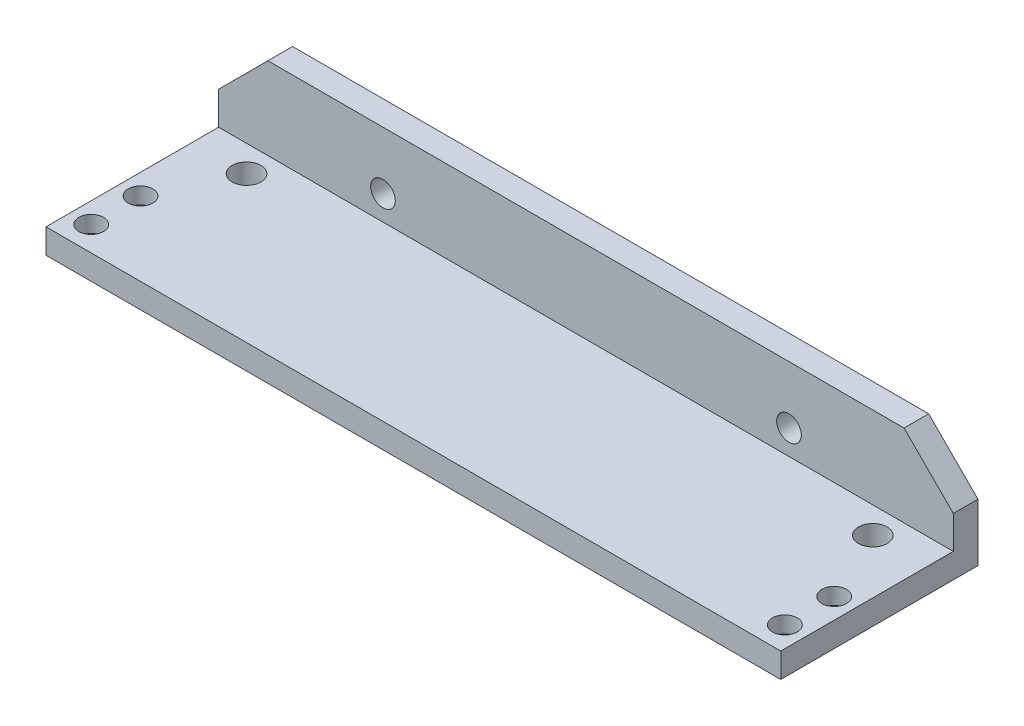
SolidWorks part; units mm, degrees
material "7075-T6, Plate (SS)"
ref_plane "Front Plane" through (0, 0, 0) normal (0, 0, 1) x (1, 0, 0)
ref_plane "Top Plane" through (0, 0, 0) normal (0, 1, 0) x (1, 0, 0)
ref_plane "Right Plane" through (0, 0, 0) normal (1, 0, 0) x (0, 0, -1)
sketch "Sketch1" plane through (0, 0, 0) normal (0, 0, 1) x (1, 0, 0)
  line L0 (-38.2511, 8.8926) -> (-38.2511, -1.1074)
  line L1 (-38.2511, -1.1074) -> (51.1489, -1.1074)
  line L2 (51.1489, -1.1074) -> (51.1489, 8.8926)
  line L3 (51.1489, 8.8926) -> (-38.2511, 8.8926)
  line L4 (-38.2511, -1.1074) -> (-38.2511, -4.1074)
  line L5 (-38.2511, -4.1074) -> (51.1489, -4.1074)
  line L6 (51.1489, -4.1074) -> (51.1489, -1.1074)
  line L7 (-38.2511, 2.8926) -> (-32.2511, 8.8926)
  line L8 (51.1489, 2.8926) -> (45.1489, 8.8926)
  circle A0 centre (-18.2511, 1.8926) radius 1.5
  circle A1 centre (31.1489, 1.8926) radius 1.5
  dimension "D2" = 3
  dimension "D3" = 3
  dimension "D1" = 89.4
  dimension "D4" = 3
  dimension "D5" = 10
  dimension "D6" = 3
  dimension "D7" = 3
  dimension "D8" = 20
  dimension "D9" = 20
  dimension "D10" = 4
  dimension "D11" = 6
  dimension "D12" = 6
  dimension "D13" = 6
extrude "Boss-Extrude1" add sketch "Sketch1" along normal blind 3 contours L2 L3 L0 L1 A1 A0 region at (6.4489, 3.7981, 0)
extrude "Boss-Extrude2" add sketch "Sketch1<3>" along normal blind 24 contours L5 L6 L1 L4 region at (6.4489, -2.6074, 0)
sketch "Sketch1<3>" plane through (0, 0, 0) normal (0, 0, 1) x (1, 0, 0) same geometry as "Sketch1"
sketch "Sketch3" plane through (0, -1.1074, 0) normal (0, 1, 0) x (1, 0, 0)
  line L0 (-38.2511, -3) -> (51.1489, -3) construction
  line L1 (45.1489, -3) -> (-32.2511, -3) construction
  line L2 (51.1489, -24) -> (51.1489, -3) construction
  line L3 (-38.2511, -24) -> (-38.2511, -3) construction
  line L4 (-38.2511, -24) -> (51.1489, -24) construction
  circle A2 centre (-31.6511, -6.2) radius 1.75
  circle A5 centre (44.5489, -6.2) radius 1.75
  circle A6 centre (-35.7511, -15) radius 1.5
  circle A7 centre (-35.7511, -21) radius 1.5
  circle A8 centre (48.6489, -15) radius 1.5
  circle A9 centre (48.6489, -21) radius 1.5
  circle A10 centre (-35.7511, -21) radius 2.25
  circle A11 centre (-35.7511, -15) radius 2.25
  circle A12 centre (48.6489, -21) radius 2.25
  circle A13 centre (48.6489, -15) radius 2.25
  dimension "D1" = 3.5
  dimension "D2" = 3.5
  dimension "D7" = 3
  dimension "D8" = 3
  dimension "D10" = 3
  dimension "D17" = 3
  dimension "D18" = 3
  dimension "D19" = 4.5
  dimension "D20" = 4.5
  dimension "D21" = 4.5
  dimension "D22" = 4.5
  dimension "D3" = 3.2
  dimension "D4" = 3.2
  dimension "D5" = 6.6
  dimension "D6" = 6.6
  dimension "D9" = 6
  dimension "D11" = 2.5
  dimension "D12" = 2.5
  dimension "D13" = 3
  dimension "D14" = 6
  dimension "D15" = 2.5
  dimension "D16" = 2.5
extrude "Cut-Extrude1" cut sketch "Sketch3" against normal up to next contours A8 | A9 | A6 | A7 | A5 | A2 region at (-35.7511, -1.1074, 15) region at (48.6489, -1.1074, 15) region at (48.6489, -1.1074, 21)
extrude "Cut-Extrude2" cut sketch "Sketch3<5>" along normal blind 1 from surface contours A11 A6 | A10 A7 | A13 | A12 region at (-37.9374, -1.1074, 21) region at (-37.9374, -1.1074, 15) starting at face at (44.5489, -4.1074, 7.95)
sketch "Sketch3<5>" plane through (0, -1.1074, 0) normal (0, 1, 0) x (1, 0, 0) same geometry as "Sketch3"
